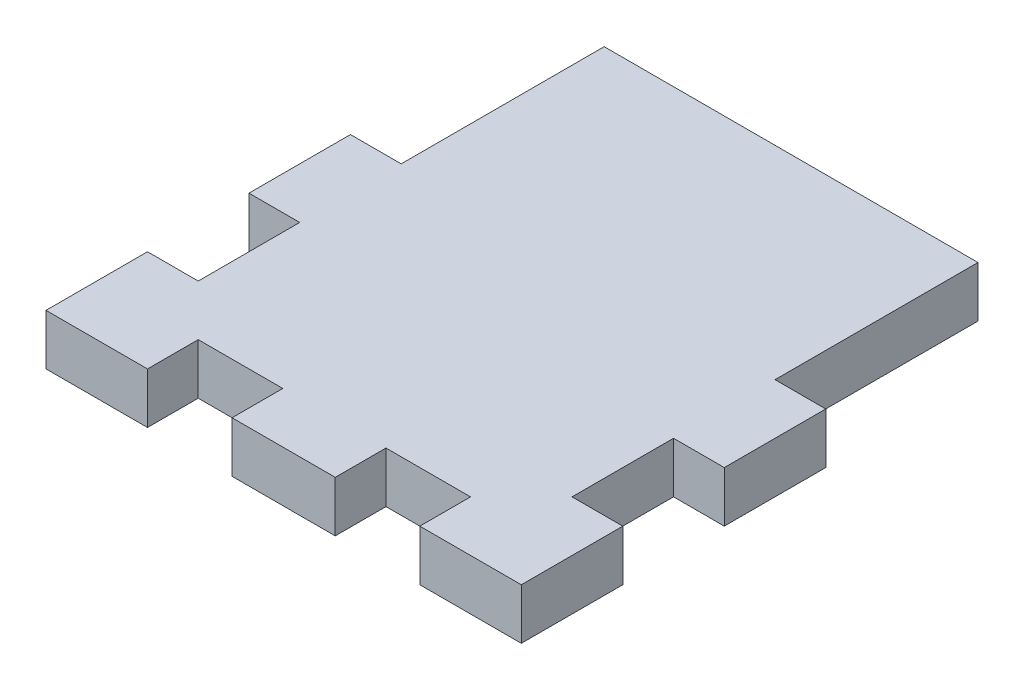
SolidWorks part; units mm, degrees
ref_plane "Plano frontal" through (0, 0, 0) normal (0, 0, 1) x (1, 0, 0)
ref_plane "Plano superior" through (0, 0, 0) normal (0, 1, 0) x (1, 0, 0)
ref_plane "Plano direito" through (0, 0, 0) normal (1, 0, 0) x (0, 0, -1)
sketch "ParedeLado2Esboco" plane through (0, 0, 0) normal (0, 1, 0) x (1, 0, 0)
  line L0 (0, 0) -> (0, 6)
  line L1 (0, 6) -> (3, 6)
  line L2 (3, 6) -> (3, 12)
  line L3 (3, 12) -> (0, 12)
  line L4 (0, 12) -> (0, 18)
  line L5 (0, 18) -> (3, 18)
  line L6 (3, 18) -> (3, 30)
  line L7 (3, 30) -> (25.1, 30)
  line L8 (25.1, 30) -> (25.1, 18)
  line L9 (25.1, 18) -> (28.1, 18)
  line L10 (28.1, 18) -> (28.1, 12)
  line L11 (28.1, 12) -> (25.1, 12)
  line L12 (25.1, 12) -> (25.1, 6)
  line L13 (25.1, 6) -> (28.1, 6)
  line L14 (28.1, 6) -> (28.1, 0)
  line L15 (28.1, 0) -> (22.1, 0)
  line L16 (22.1, 0) -> (22.1, 3)
  line L17 (22.1, 3) -> (17.1, 3)
  line L18 (17.1, 3) -> (17.1, 0)
  line L19 (17.1, 0) -> (11, 0)
  line L20 (11, 0) -> (11, 3)
  line L21 (11, 3) -> (6, 3)
  line L22 (6, 3) -> (6, 0)
  line L23 (6, 0) -> (0, 0)
  dimension "D1" = 28.1
  dimension "D2" = 3
  dimension "D3" = 3
  dimension "D4" = 3
  dimension "D5" = 30
  dimension "D6" = 6
  dimension "D7" = 6
  dimension "D8" = 6
  dimension "D9" = 6
  dimension "D10" = 6
  dimension "D11" = 5
  dimension "D12" = 5
extrude "ParedeLado2" add sketch "ParedeLado2Esboco" along normal blind 3
